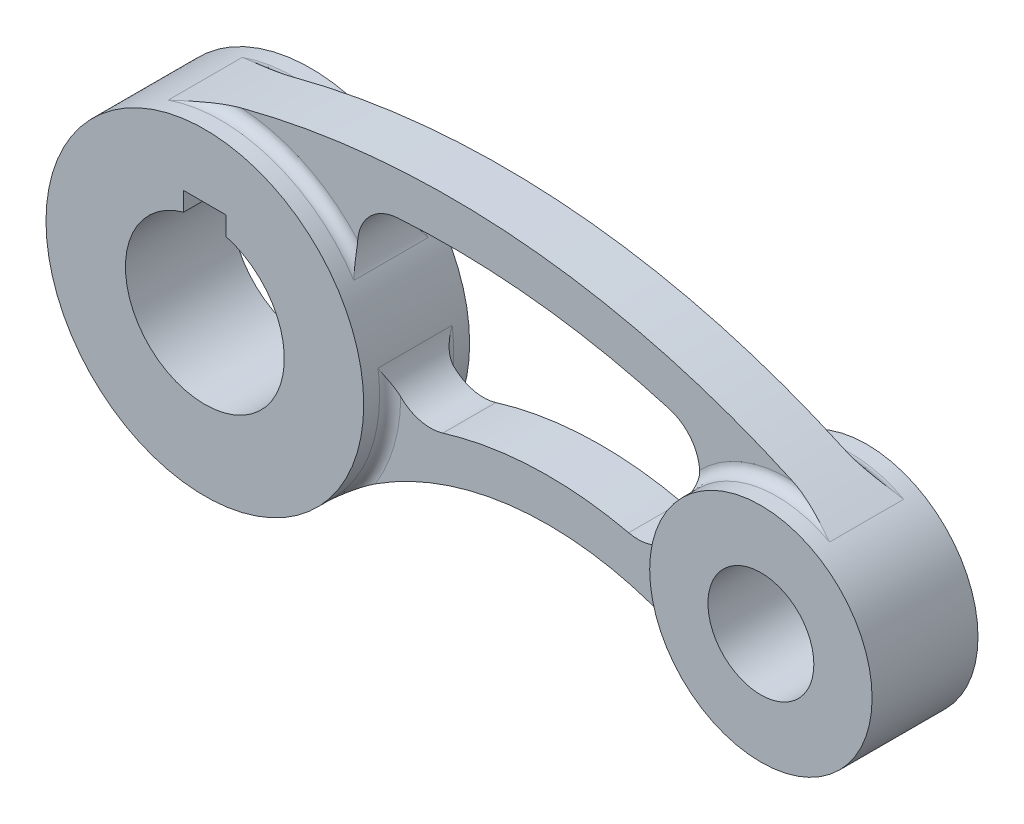
SolidWorks part; units mm, degrees
ref_plane "Front Plane" through (0, 0, 0) normal (0, 0, 1) x (1, 0, 0)
ref_plane "Top Plane" through (0, 0, 0) normal (0, 1, 0) x (1, 0, 0)
ref_plane "Right Plane" through (0, 0, 0) normal (1, 0, 0) x (0, 0, -1)
sketch "Sketch1" plane through (0, 0, 0) normal (0, 0, 1) x (1, 0, 0)
  line L0 (0, 0) -> (-105, 0) construction
  line L1 (-105, 0) -> (-105, 26.5646) construction
  line L2 (-109, 14.4568) -> (-109, 18)
  line L3 (-109, 18) -> (-101, 18)
  line L4 (-101, 18) -> (-101, 14.4568)
  arc A0 (-17.7699, 11.1907) -> (-20.4072, 4.9543) centre (0, 0) ccw
  circle A1 centre (0, 0) radius 10
  arc A2 (-114.936, 28.3068) -> (-85.0571, -22.4117) centre (-105, 0) ccw
  arc A3 (-109, 14.4568) -> (-101, 14.4568) centre (-105, 0) ccw
  arc A4 (-114.936, 28.3068) -> (9.9672, 18.4839) centre (-63.6, -117.9451) cw
  arc A5 (-11.7111, -17.4313) -> (-85.0571, -22.4117) centre (-45.1714, -67.235) ccw
  arc A6 (-73.6998, 28.7076) -> (-22.2912, 23.1315) centre (-63.6, -117.9451) cw
  arc A7 (-29.9698, -0.9559) -> (-65.053, -2.2063) centre (-45.1714, -67.235) ccw
  arc A8 (-112.2864, 20.7583) -> (6.1701, 11.4424) centre (-63.6, -117.9451) cw construction
  arc A9 (-7.2497, -10.7908) -> (-90.3752, -16.4352) centre (-45.1714, -67.235) ccw construction
  arc A10 (-75.3095, 4.298) -> (-79.8554, 16.363) centre (-105, 0) ccw
  arc A11 (-11.7111, -17.4313) -> (9.9672, 18.4839) centre (0, 0) ccw
  arc A12 (-29.9698, -0.9559) -> (-20.4072, 4.9543) centre (-28.1814, 6.8416) ccw
  arc A13 (-22.2912, 23.1315) -> (-17.7699, 11.1907) centre (-24.5393, 15.4538) cw
  arc A14 (-73.6998, 28.7076) -> (-79.8554, 16.363) centre (-73.1501, 20.7265) ccw
  arc A15 (-65.053, -2.2063) -> (-75.3095, 4.298) centre (-67.392, 5.4441) cw
  circle A16 centre (-105, 0) radius 30
  circle A17 centre (0, 0) radius 21
  point P29 (-75.7075, -6.4769)
  dimension "D1" = 30
  dimension "D2" = 60
  dimension "D3" = 42
  dimension "D4" = 20
  dimension "D6" = 155
  dimension "D7" = 60
  dimension "D10" = 8
  dimension "D11" = 8
  dimension "D5" = 105
  dimension "D12" = 8
  dimension "D13" = 33
  dimension "D8" = 8
  dimension "D9" = 8
extrude "Boss-Extrude1" add sketch "Sketch1" along normal blind 10 and the other way blind 10 contours A10 A16 A2 A3 L2 L3 L4 | A11 A17 A0 A1 region at (-5.1892, 19.7352, 0) region at (-95.6045, 27.5959, 0)
extrude "Boss-Extrude2" add sketch "Sketch1<4>" along normal blind 5 and the other way blind 5 contours A17 A12 A7 A15 A16 A5 | A17 A4 A16 A14 A6 A13 region at (-51.1222, 29.2221, 0) region at (-48.8867, -5.6979, 0)
sketch "Sketch1<4>" plane through (0, 0, 0) normal (0, 0, 1) x (1, 0, 0) same geometry as "Sketch1"
fillet "Fillet1" radius 2 8 edges at (-5.3403, 20.3096, -5) (-95.331, 28.3991, -5) (-5.3403, 20.3096, 5) (-19.5749, -7.6043, 5) (-76.8181, -10.285, 5) (-19.5749, -7.6043, -5) (-76.8181, -10.285, -5) (-95.331, 28.3991, 5)
